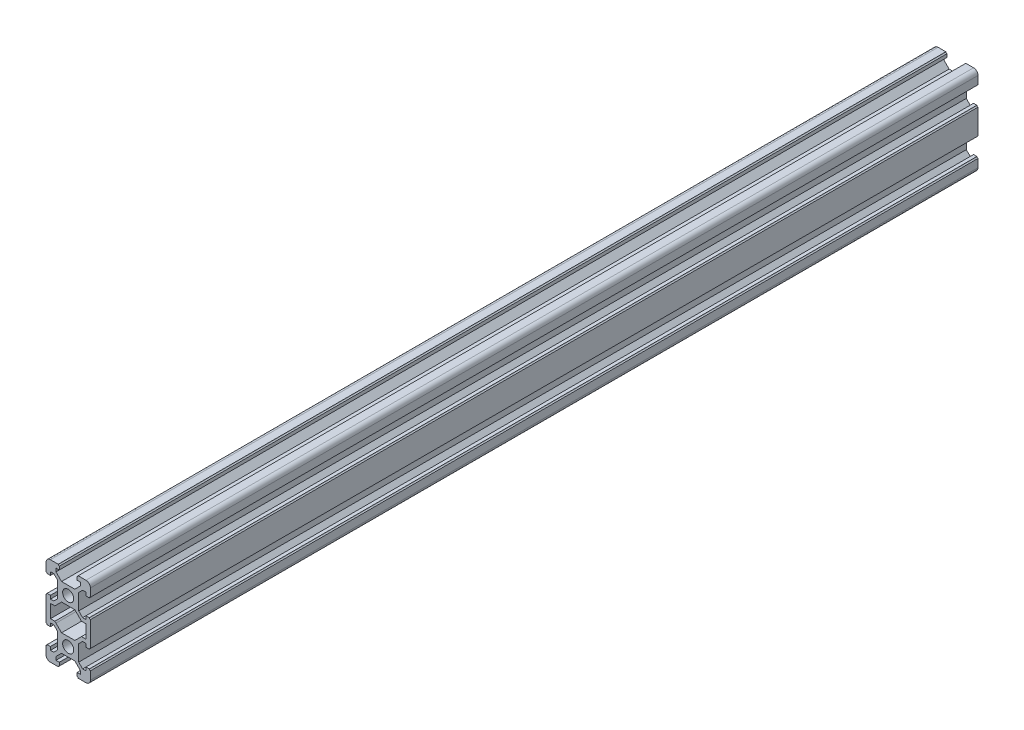
SolidWorks part; units mm, degrees
ref_plane "Спереди" through (0, 0, 0) normal (0, 0, 1) x (1, 0, 0)
ref_plane "Сверху" through (0, 0, 0) normal (0, 1, 0) x (1, 0, 0)
ref_plane "Справа" through (0, 0, 0) normal (1, 0, 0) x (0, 0, -1)
sketch "Эскиз1" plane through (0, 0, 0) normal (0, 0, 1) x (1, 0, 0)
  line L0 (0, 0) -> (10, 0) construction
  line L1 (10, 0) -> (10, 20) construction
  line L2 (10, 20) -> (0, 20) construction
  line L3 (0, 20) -> (0, 0) construction
  line L4 (0, 14) -> (3, 14)
  line L5 (3, 14) -> (5.5, 16.5)
  line L6 (5.5, 16.5) -> (5.5, 18)
  line L7 (5.5, 18) -> (4, 18)
  line L8 (4, 18) -> (4, 20)
  line L9 (4, 20) -> (10, 20)
  line L10 (10, 20) -> (10, 13.8581)
  line L11 (10, 13.8581) -> (8, 13.8581)
  line L12 (8, 13.8581) -> (8, 15.3581)
  line L13 (8, 15.3581) -> (6.5, 15.3581)
  line L14 (6.5, 15.3581) -> (4.7405, 13.5985)
  line L15 (5.5, 17.25) -> (0, 17.25) construction
  line L16 (4, 19) -> (0, 19) construction
  line L17 (8, 14.6081) -> (0, 14.6081) construction
  line L18 (0, 10) -> (10, 10) construction
  line L19 (1.5, 14) -> (1.5, 10) construction
  line L20 (4.7405, 13.5985) -> (4.7405, 6.4015)
  line L21 (3, 6) -> (5.5, 3.5)
  line L22 (0, 6) -> (3, 6)
  line L23 (8, 4.6419) -> (6.5, 4.6419)
  line L24 (6.5, 4.6419) -> (4.7405, 6.4015)
  line L25 (10, 0) -> (10, 6.1419)
  line L26 (10, 6.1419) -> (8, 6.1419)
  line L27 (8, 6.1419) -> (8, 4.6419)
  line L28 (5.5, 3.5) -> (5.992, 3)
  line L29 (8, 0) -> (8, 3)
  line L30 (8, 0) -> (10, 0)
  line L31 (0, 6) -> (0, 7.5)
  line L32 (0, 12.5) -> (0, 14)
  line L33 (8, 3) -> (5.992, 3)
  line L34 (5.992, 3) -> (5.992, 0) construction
  circle A0 centre (0, 10) radius 2.5
  circle A4 centre (10, 6.1419) radius 0.5
  circle A5 centre (10, 13.8581) radius 0.5
  circle A6 centre (4, 20) radius 0.5
  point P34 (4.7405, 10)
  dimension "D3" = 5
  dimension "D11" = 1
  dimension "D12" = 1
  dimension "D13" = 1
  dimension "D1" = 20
  dimension "D2" = 10
  dimension "D4" = 5.5
  dimension "D5" = 4
  dimension "D6" = 8
  dimension "D7" = 1.5
  dimension "D8" = 4
  dimension "D9" = 135
  dimension "D10" = 3
extrude "Бобышка-Вытянуть1" add sketch "Эскиз1" along normal blind 200 and the other way blind 200 contours A0 L31 L22 L21 L28 L30 L25 L26 L27 L23 L24 L20 L14 L13 L12 L11 L10 L9 L8 L7 L6 L5 L4 L32 region at (1.5, 13.7764, 0)
mirror "Зеркальное отражение1" about plane through (0, 0, 0) normal (1, 0, 0) of "Бобышка-Вытянуть1"
mirror "Зеркальное отражение2" about plane through (0, 0, 0) normal (0, 1, 0) of "Зеркальное отражение1"
fillet "Скругление1" radius 2 4 edges at (-10, -20, 0) (10, -20, 0) (10, 20, 0) (-10, 20, 0)
ref_plane "Плоскость1" through (0, -10, 0) normal (0, -1, 0) x (-1, 0, 0)
